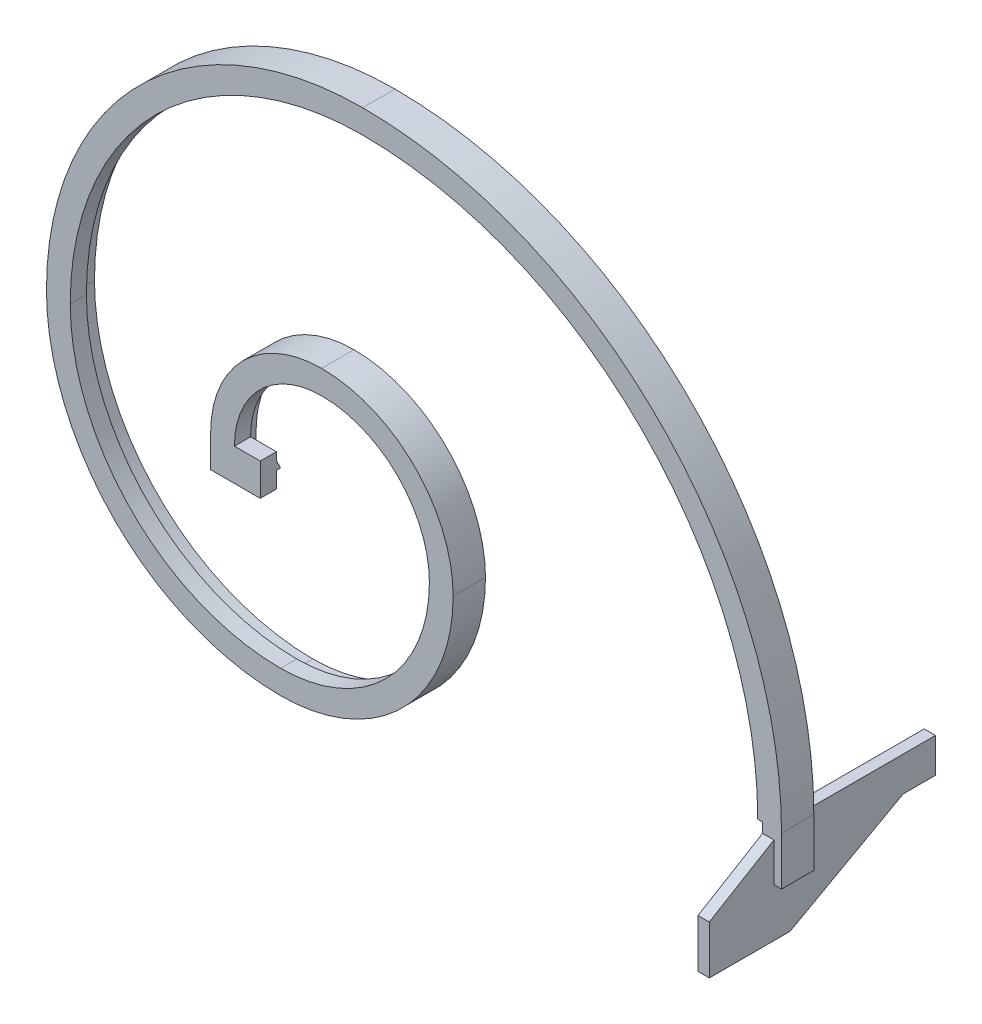
SolidWorks part; units mm, degrees
ref_plane "Front" through (0, 0, 0) normal (0, 0, 1) x (1, 0, 0)
ref_plane "Top" through (0, 0, 0) normal (0, 1, 0) x (1, 0, 0)
ref_plane "Right" through (0, 0, 0) normal (1, 0, 0) x (0, 0, -1)
sketch "Sketch2" plane through (0, 0, 0) normal (0, 0, 1) x (1, 0, 0)
  line L0 (-28.4875, 0) -> (-28.4875, -10)
  line L1 (-28.4875, -10) -> (-31.9875, -10)
  line L2 (-31.9875, -10) -> (-31.9875, 0)
  line L3 (139.9375, -19.05) -> (136.4375, -19.05)
  arc A0 (-28.4875, 0) -> (0, 28.4875) centre (0, 0) cw
  arc A1 (0, 28.4875) -> (34.8375, -6.35) centre (0, -6.35) cw
  arc A2 (34.8375, -6.35) -> (-12.7, -53.8875) centre (-12.7, -6.35) cw
  arc A3 (-12.7, -53.8875) -> (-79.2875, 12.7) centre (-12.7, 12.7) cw
  arc A4 (-79.2875, 12.7) -> (12.7, 104.6875) centre (12.7, 12.7) cw
  arc A5 (12.7, 104.6875) -> (136.4375, -19.05) centre (12.7, -19.05) cw
  arc A6 (-31.9875, 0) -> (0, 31.9875) centre (0, 0) cw
  arc A7 (0, 31.9875) -> (38.3375, -6.35) centre (0, -6.35) cw
  arc A8 (38.3375, -6.35) -> (-12.7, -57.3875) centre (-12.7, -6.35) cw
  arc A9 (-12.7, -57.3875) -> (-82.7875, 12.7) centre (-12.7, 12.7) cw
  arc A10 (-82.7875, 12.7) -> (12.7, 108.1875) centre (12.7, 12.7) cw
  arc A11 (12.7, 108.1875) -> (139.9375, -19.05) centre (12.7, -19.05) cw
extrude "Extrude2" add sketch "Sketch2" along normal blind 5
sketch "Sketch3" plane through (0, 0, 5) normal (0, 0, 1) x (1, 0, 0)
  line L0 (-26.9875, 0) -> (-26.9875, -10)
  line L1 (-26.9875, -10) -> (-31.9875, -10)
  line L2 (134.9375, -19.05) -> (139.9375, -19.05)
  line L3 (-31.9875, -10) -> (-31.9875, 0)
  arc A0 (-31.9875, 0) -> (0, 31.9875) centre (0, 0) cw
  arc A1 (-26.9875, 0) -> (0, 26.9875) centre (0, 0) cw
  arc A2 (0, 26.9875) -> (33.3375, -6.35) centre (0, -6.35) cw
  arc A3 (0, 31.9875) -> (38.3375, -6.35) centre (0, -6.35) cw
  arc A5 (33.3375, -6.35) -> (-12.7, -52.3875) centre (-12.7, -6.35) cw
  arc A6 (-12.7, -52.3875) -> (-77.7875, 12.7) centre (-12.7, 12.7) cw
  arc A7 (-77.7875, 12.7) -> (12.7, 103.1875) centre (12.7, 12.7) cw
  arc A8 (12.7, 103.1875) -> (134.9375, -19.05) centre (12.7, -19.05) cw
  arc A9 (38.3375, -6.35) -> (-12.7, -57.3875) centre (-12.7, -6.35) cw
  arc A10 (-12.7, -57.3875) -> (-82.7875, 12.7) centre (-12.7, 12.7) cw
  arc A11 (-82.7875, 12.7) -> (-12.7, -57.3875) centre (-12.7, 12.7) ccw construction
  arc A12 (-82.7875, 12.7) -> (12.7, 108.1875) centre (12.7, 12.7) cw
  arc A13 (12.7, 108.1875) -> (139.9375, -19.05) centre (12.7, -19.05) cw
extrude "Extrude3" add sketch "Sketch3" along normal blind 5
sketch "Sketch4" plane through (-28.4875, 0, 0) normal (1, 0, 0) x (0, 0, -1)
  line L0 (-5, -2.4) -> (-1.2, -10)
  line L1 (-5, -19.05) -> (-5, 104.6875) construction
  line L2 (-5, -10) -> (0, -10) construction
  line L3 (-1.2, -10) -> (-5, -10)
  line L4 (-5, -10) -> (-5, -2.4)
extrude "Extrude4" add sketch "Sketch4" along normal blind 9.5
sketch "Sketch6" plane through (-18.9875, 0, 0) normal (1, 0, 0) x (0, 0, -1)
  line L0 (-5, -5) -> (-3.7, -5)
  line L1 (-5, -19.05) -> (-5, 104.6875) construction
  line L2 (-1.2, -10) -> (-5, -2.4) construction
  line L3 (-3.7, -5) -> (-1.2, -10)
  line L4 (-1.2, -10) -> (-5, -10)
  line L5 (-5, -10) -> (-5, -5)
extrude "Cut-Extrude1" cut sketch "Sketch6" against normal blind 8
sketch "Sketch7" plane through (-26.9875, 0, 0) normal (1, 0, 0) x (0, 0, -1)
  line L0 (-5, 0) -> (-10, 0)
  line L1 (-10, 0) -> (-10, -10)
  line L2 (-10, -10) -> (-5, -10)
  line L3 (-5, -19.05) -> (-5, 104.6875) construction
  line L4 (-5, -10) -> (-5, 0)
extrude "Extrude5" add sketch "Sketch7" along normal blind 8
sketch "Sketch8" plane through (0, -19.05, 0) normal (0, -1, 0) x (1, 0, 0)
  line L0 (139.9375, 10) -> (139.9375, 0)
  line L1 (139.9375, 0) -> (136.4375, 0)
  line L2 (136.4375, 0) -> (136.4375, 10)
  line L3 (134.9375, 10) -> (139.9375, 10) construction
  line L4 (136.4375, 10) -> (139.9375, 10)
extrude "Extrude6" add sketch "Sketch8" along normal blind 30
sketch "Sketch9" plane through (0, 0, 10) normal (0, 0, 1) x (1, 0, 0)
  line L0 (136.4375, -19.05) -> (139.9375, -19.05)
  line L1 (139.9375, -19.05) -> (139.9375, -49.05)
  line L2 (139.9375, -49.05) -> (136.4375, -49.05)
  line L3 (136.4375, -49.05) -> (136.4375, -19.05)
extrude "Extrude7" add sketch "Sketch9" along normal blind 20
sketch "Sketch11" plane through (0, 0, 0) normal (0, 0, -1) x (-1, 0, 0)
  line L0 (-139.9375, -19.05) -> (-136.4375, -19.05)
  line L1 (-136.4375, -19.05) -> (-136.4375, -49.05)
  line L2 (-136.4375, -49.05) -> (-139.9375, -49.05)
  line L3 (-139.9375, -49.05) -> (-139.9375, -19.05)
extrude "Extrude8" add sketch "Sketch11" along normal blind 30
sketch "Sketch10" plane through (139.9375, 0, 0) normal (1, 0, 0) x (0, 0, -1)
  line L0 (-5, -49.05) -> (30, -29.7287)
  line L1 (-30, -49.05) -> (-30, -19.05) construction
  line L2 (30, -49.05) -> (-30, -49.05) construction
  line L3 (-30, -34.05) -> (-30, -19.05)
  line L4 (-30, -19.05) -> (-10, -19.05)
  line L5 (-10, -19.05) -> (-10, -22.05)
  line L6 (-10, -22.05) -> (-30, -34.05)
  line L7 (30, -19.05) -> (30, -49.05) construction
  line L8 (30, -29.7287) -> (30, -49.05)
  line L9 (30, -49.05) -> (-5, -49.05)
extrude "Cut-Extrude2" cut sketch "Sketch10" against normal blind 5
sketch "Sketch12" plane through (0, 0, -30) normal (0, 0, -1) x (-1, 0, 0)
  line L0 (-139.9375, -19.05) -> (-136.4375, -19.05)
  line L1 (-136.4375, -19.05) -> (-136.4375, -29.7287)
  line L2 (-139.9375, -19.05) -> (-139.9375, -29.7287)
  line L4 (-136.4375, -29.7287) -> (-139.9375, -29.7287)
extrude "Extrude9" add sketch "Sketch12" along normal blind 10
sketch "Sketch14" plane through (0, 0, 10) normal (0, 0, 1) x (1, 0, 0)
  line L0 (-34.3375, 0) -> (-34.3375, -10)
  line L1 (-31.9875, 0) -> (-31.9875, -10)
  line L2 (-31.9875, 0) -> (-31.9875, -10) construction
  line L3 (-31.9875, -10) -> (-34.3375, -10)
  line L4 (142.2875, -19.0647) -> (142.2875, -34.05)
  line L5 (142.2875, -34.05) -> (139.9375, -34.05)
  line L6 (139.9375, -34.05) -> (139.9375, -19.0647)
  arc A0 (-34.3375, 0) -> (0, 34.3375) centre (0, 0) cw
  arc A1 (0, 34.3375) -> (40.6875, -6.35) centre (0, -6.35) cw
  arc A2 (40.6875, -6.35) -> (-12.7, -59.7375) centre (-12.7, -6.35) cw
  arc A3 (-12.7, -59.7375) -> (-85.1375, 12.7419) centre (-12.7, 12.7) cw
  arc A4 (-31.9875, 0) -> (0, 31.9875) centre (0, 0) cw
  arc A5 (0, 31.9875) -> (38.3375, -6.35) centre (0, -6.35) cw
  arc A6 (38.3375, -6.35) -> (-12.7, -57.3875) centre (-12.7, -6.35) cw
  arc A7 (-12.7, -57.3875) -> (-82.7875, 12.7406) centre (-12.7, 12.7) cw
  arc A8 (-82.7875, 12.7406) -> (12.7, 108.1728) centre (12.7, 12.6853) cw
  arc A9 (-85.1375, 12.7419) -> (12.7, 110.5228) centre (12.7, 12.6853) cw
  arc A10 (12.7, 108.1728) -> (139.9375, -19.0647) centre (12.7, -19.0647) cw
  arc A11 (12.7, 110.5228) -> (142.2875, -19.0647) centre (12.7, -19.0647) cw
extrude "Extrude10" add sketch "Sketch14" against normal blind 10
sketch "Sketch15" plane through (-34.3375, 0, 0) normal (-1, 0, 0) x (0, 0, 1)
  line L0 (0, 14) -> (0, -10)
  line L1 (0, 110.5228) -> (0, 12.7419) construction
  line L2 (0, -10) -> (1.2, -10)
  line L3 (1.2, -10) -> (0, 14)
extrude "Cut-Extrude3" cut sketch "Sketch15" against normal blind 15
sketch "Sketch16" plane through (0, 0, 0) normal (0, 0, -1) x (-1, 0, 0)
  line L0 (28.4875, 0) -> (29.4875, 0)
  line L1 (-137.4375, -19.05) -> (-136.4375, -34.05)
  line L4 (-136.4375, -34.05) -> (-136.4375, -19.05)
  arc A0 (28.4875, 0) -> (0, 28.4875) centre (0, 0) ccw
  arc A1 (0, 28.4875) -> (-34.8375, -6.35) centre (0, -6.35) ccw
  arc A2 (-34.8375, -6.35) -> (12.7, -53.8875) centre (12.7, -6.35) ccw
  arc A3 (12.7, -53.8875) -> (79.2875, 12.7) centre (12.7, 12.7) ccw
  arc A4 (79.2875, 12.7) -> (-12.7, 104.6875) centre (-12.7, 12.7) ccw
  arc A5 (-12.7, 104.6875) -> (-136.4375, -19.05) centre (-12.7, -19.05) ccw
  arc A6 (29.4875, 0) -> (0, 29.4875) centre (0, 0) ccw
  arc A7 (0, 29.4875) -> (-35.8375, -6.35) centre (0, -6.35) ccw
  arc A8 (-35.8375, -6.35) -> (12.7, -54.8875) centre (12.7, -6.35) ccw
  arc A9 (12.7, -54.8875) -> (80.2875, 12.7) centre (12.7, 12.7) ccw
  arc A10 (80.2875, 12.7) -> (-12.7, 105.6875) centre (-12.7, 12.7) ccw
  arc A11 (-12.7, 105.6875) -> (-137.4375, -19.05) centre (-12.7, -19.05) ccw
extrude "Cut-Extrude4" cut sketch "Sketch16" against normal blind 5
sketch "Sketch17" plane through (-28.4875, 0, 0) normal (1, 0, 0) x (0, 0, -1)
  line L0 (-5, 0) -> (-5, -2.4)
  line L1 (-5, -2.4) -> (-1.2, -10)
  line L2 (-1.2, -10) -> (0, -10)
  line L3 (0, -19.0647) -> (0, 110.5228) construction
  line L4 (0, -10) -> (0, 0)
  line L5 (0, 0) -> (-5, 0)
extrude "Cut-Extrude5" cut sketch "Sketch17" against normal blind 1
